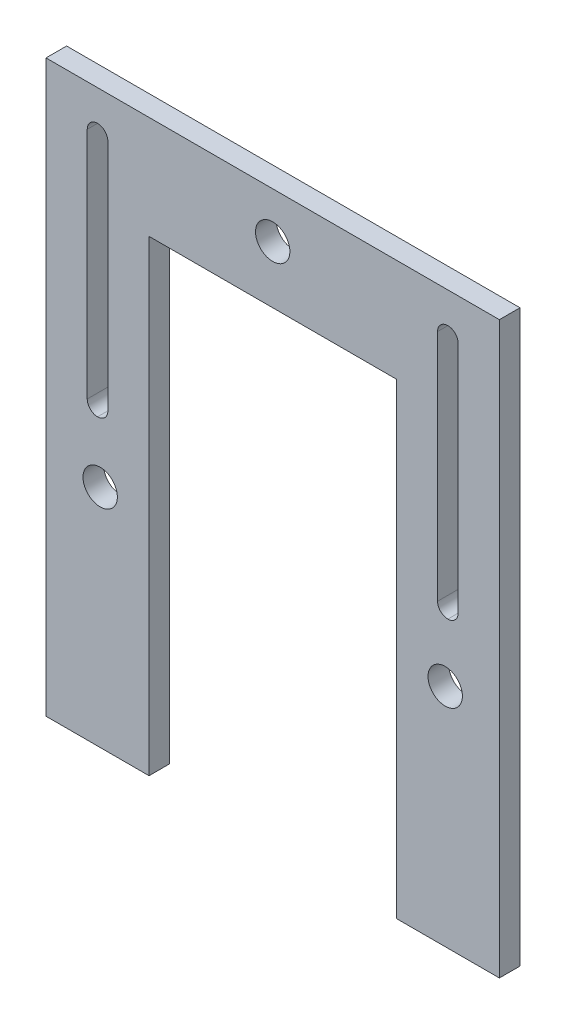
SolidWorks part; units mm, degrees
ref_plane "前视基准面" through (0, 0, 0) normal (0, 0, 1) x (1, 0, 0)
ref_plane "上视基准面" through (0, 0, 0) normal (0, 1, 0) x (1, 0, 0)
ref_plane "右视基准面" through (0, 0, 0) normal (1, 0, 0) x (0, 0, -1)
sketch "草图1" plane through (0, 0, 0) normal (0, 0, 1) x (1, 0, 0)
  line L0 (0, 28.0304) -> (0, -31.1401) construction
  line L1 (-18, 19.6935) -> (18, 19.6935)
  line L2 (18, 19.6935) -> (18, -48.3065)
  line L3 (18, -48.3065) -> (33, -48.3065)
  line L4 (33, -48.3065) -> (33, 34.6935)
  line L5 (33, 34.6935) -> (-33, 34.6935)
  line L6 (-33, -48.3065) -> (-33, 34.6935)
  line L7 (-18, -48.3065) -> (-33, -48.3065)
  line L8 (-18, 19.6935) -> (-18, -48.3065)
  circle A1 centre (0, 28.0304) radius 2.5
  circle A2 centre (25.1147, -15.4696) radius 2.5
  circle A3 centre (-25.1147, -15.4696) radius 2.5
  point P10 (0, 34.6935)
  point P13 (0, 19.6935)
  point P22 (0, -0.9696)
  dimension "D5" = 3
  dimension "D1" = 66
  dimension "D2" = 83
  dimension "D3" = 15
  dimension "D4" = 15
  dimension "D6" = 29
extrude "凸台-拉伸1" add sketch "草图1" along normal blind 3
sketch "草图2" plane through (0, 0, 3) normal (0, 0, 1) x (1, 0, 0)
  line L0 (0, 34.6935) -> (0, -51.8659) construction
  line L1 (33, 34.6935) -> (-33, 34.6935) construction
  line L2 (25.5, -48.3065) -> (25.5, 34.6935) construction
  line L3 (18, -48.3065) -> (33, -48.3065) construction
  line L4 (-25.5, -48.3065) -> (-25.5, 34.6935) construction
  line L5 (-33, -48.3065) -> (-18, -48.3065) construction
  line L6 (27, -6.8065) -> (24, -6.8065)
  line L7 (-27, 30.1935) -> (-24, 30.1935)
  line L8 (-27, 30.1935) -> (-27, -6.8065)
  line L9 (-27, -6.8065) -> (-24, -6.8065)
  line L10 (-24, 30.1935) -> (-24, -6.8065)
  line L11 (-27, 30.1935) -> (-24, -6.8065) construction
  line L12 (-27, -6.8065) -> (-24, 30.1935) construction
  line L13 (24, 30.1935) -> (24, -6.8065)
  line L14 (27, 30.1935) -> (27, -6.8065)
  line L16 (27, 30.1935) -> (24, 30.1935)
  point P11 (-25.5, 11.6935)
  dimension "D1" = 37
  dimension "D2" = 3
  dimension "D3" = 23
extrude "切除-拉伸1" cut sketch "草图2" against normal through all
fillet "圆角1" radius 1.5 8 edges at (27, 30.1935, 1.5) (24, 30.1935, 1.5) (24, -6.8065, 1.5) (27, -6.8065, 1.5) (-24, -6.8065, 1.5) (-27, -6.8065, 1.5) (-24, 30.1935, 1.5) (-27, 30.1935, 1.5)
